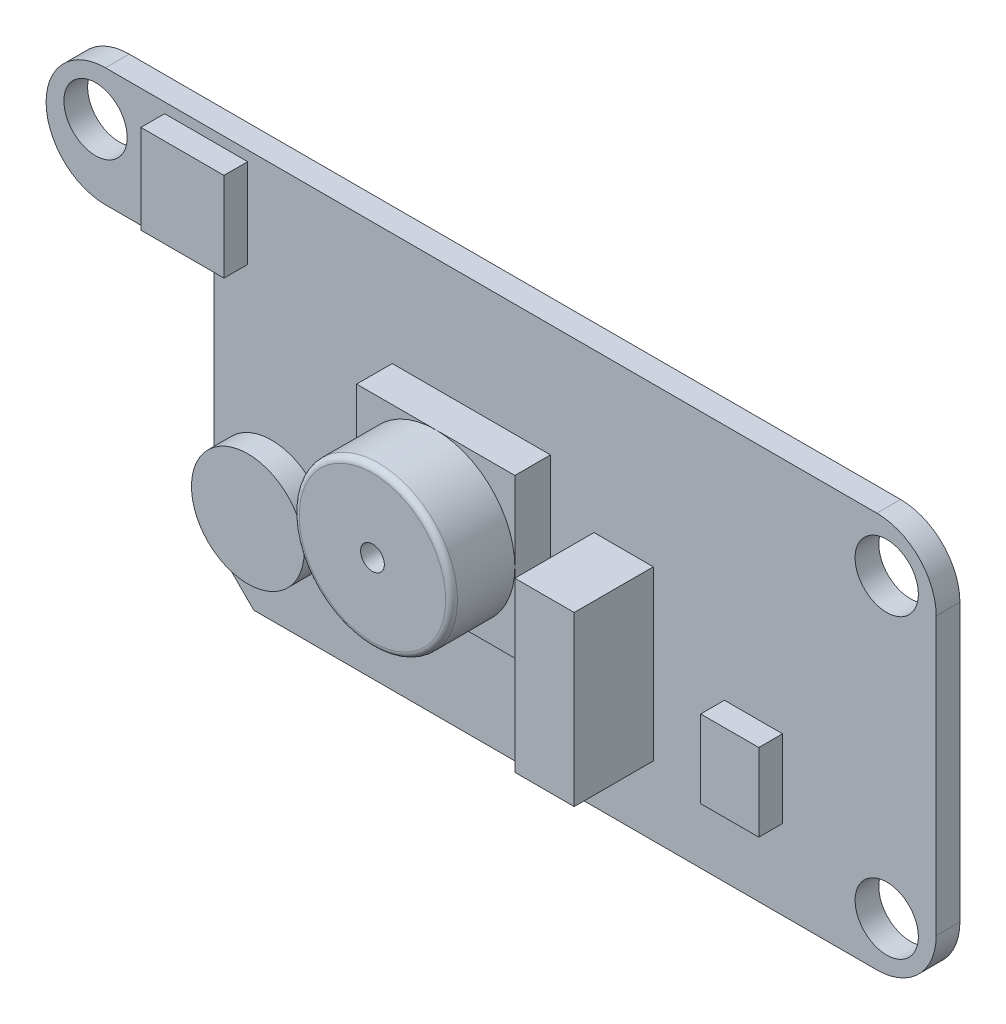
SolidWorks part; units mm, degrees
ref_plane "Front Plane" through (0, 0, 0) normal (0, 0, 1) x (1, 0, 0)
ref_plane "Top Plane" through (0, 0, 0) normal (0, 1, 0) x (1, 0, 0)
ref_plane "Right Plane" through (0, 0, 0) normal (1, 0, 0) x (0, 0, -1)
sketch "Sketch1" plane through (0, 0, 0) normal (0, 0, 1) x (1, 0, 0)
  line L0 (34, 2.5) -> (34, 17.5) construction
  line L1 (0, 0) -> (36.5, 0)
  line L2 (0, 0) -> (0, 14)
  line L3 (0, 20) -> (36.5, 20)
  line L4 (36.5, 0) -> (36.5, 20)
  line L5 (0, 20) -> (-8.5, 20)
  line L7 (0, 14) -> (-8.5, 14)
  line L8 (-8.5, 20) -> (-8.5, 14)
  line L9 (-6, 17.5) -> (33.3159, 17.5) construction
  circle A0 centre (34, 17.5) radius 1.6
  circle A1 centre (34, 2.5) radius 1.6
  circle A2 centre (-6, 17.5) radius 1.6
  dimension "D5" = 3.2
  dimension "D7" = 2.5
  dimension "D1" = 20
  dimension "D2" = 36.5
  dimension "D3" = 6
  dimension "D4" = 8.5
  dimension "D6" = 2.5
  dimension "D8" = 2.5
  dimension "D9" = 2.5
extrude "Boss-Extrude1" add sketch "Sketch1" along normal blind 1.2 contours L5 L8 L7 L2 L1 L4 L3 A2 A1 A0 region at (16.6569, 10.392, 0)
sketch "Sketch2" plane through (0, 0, 1.2) normal (0, 0, 1) x (1, 0, 0)
  line L0 (0, 0) -> (0, 14) construction
  line L1 (-2.5081, 19.4854) -> (1.6919, 19.4854)
  line L2 (-2.5081, 19.4854) -> (-2.5081, 14.9854)
  line L3 (-2.5081, 14.9854) -> (1.6919, 14.9854)
  line L4 (1.6919, 19.4854) -> (1.6919, 14.9854)
  line L5 (25.795, 7.9554) -> (28.7329, 7.9554)
  line L6 (25.795, 7.9554) -> (25.795, 4.0281)
  line L7 (25.795, 4.0281) -> (28.7329, 4.0281)
  line L8 (28.7329, 7.9554) -> (28.7329, 4.0281)
  circle A0 centre (2.9, 5.0499) radius 2.85
  dimension "D3" = 5.7
  dimension "D1" = 4.2
  dimension "D2" = 4.5
  dimension "D4" = 2.9
extrude "Boss-Extrude2" add sketch "Sketch2" along normal blind 1.2 contours A0 | L8 L5 L6 L7 | L3 L4 L1 L2 region at (27.264, 5.9918, 1.2) region at (2.9, 5.0499, 1.2)
sketch "Sketch3" plane through (0, 0, 1.2) normal (0, 0, 1) x (1, 0, 0)
  line L0 (0, 0) -> (0, 14) construction
  line L1 (9, 14.3) -> (17, 14.3)
  line L2 (9, 14.3) -> (9, 6.3)
  line L3 (9, 6.3) -> (17, 6.3)
  line L4 (17, 14.3) -> (17, 6.3)
  line L5 (36.5, 20) -> (-8.5, 20) construction
  dimension "D1" = 9
  dimension "D2" = 5.7
  dimension "D3" = 8
  dimension "D4" = 8
extrude "Boss-Extrude3" add sketch "Sketch3" along normal blind 1.8
sketch "Sketch4" plane through (0, 0, 3) normal (0, 0, 1) x (1, 0, 0)
  line L0 (9, 14.3) -> (17, 6.3) construction
  line L1 (9, 6.3) -> (17, 6.3) construction
  circle A0 centre (13, 10.3) radius 4
extrude "Boss-Extrude4" add sketch "Sketch4" along normal blind 3.2
sketch "Sketch5" plane through (0, 0, 6.2) normal (0, 0, 1) x (1, 0, 0)
  circle A0 centre (13, 10.3) radius 0.6
extrude "Cut-Extrude1" cut sketch "Sketch5" against normal blind 1
sketch "Sketch7" plane through (0, 0, 0) normal (0, 0, -1) x (-1, 0, 0)
  line L0 (0, 0) -> (0, 14) construction
  line L1 (-14, 14.5) -> (-7, 14.5)
  line L2 (-14, 14.5) -> (-14, 7.5)
  line L3 (-14, 7.5) -> (-7, 7.5)
  line L4 (-7, 14.5) -> (-7, 7.5)
  line L5 (0, 0) -> (-36.5, 0) construction
  line L7 (-23.0048, 2.8546) -> (-19.2766, 2.8546)
  line L8 (-23.0048, 2.8546) -> (-23.0048, 1.093)
  line L9 (-23.0048, 1.093) -> (-19.2766, 1.093)
  line L10 (-19.2766, 2.8546) -> (-19.2766, 1.093)
  line L11 (-23.0048, 3.6067) -> (-19.2766, 3.6067)
  line L12 (-23.0048, 3.6067) -> (-23.0048, 5.3113)
  line L13 (-23.0048, 5.3113) -> (-19.2766, 5.3113)
  line L14 (-19.2766, 3.6067) -> (-19.2766, 5.3113)
  line L15 (-21.1407, 17.7064) -> (-17.5374, 17.7064)
  line L16 (-21.1407, 17.7064) -> (-21.1407, 15.938)
  line L17 (-21.1407, 15.938) -> (-17.5374, 15.938)
  line L18 (-17.5374, 17.7064) -> (-17.5374, 15.938)
  line L19 (-8.0118, 5.8312) -> (-4.6597, 5.8312)
  line L20 (-8.0118, 5.8312) -> (-8.0118, 4.0988)
  line L21 (-8.0118, 4.0988) -> (-4.6597, 4.0988)
  line L22 (-4.6597, 5.8312) -> (-4.6597, 4.0988)
  line L23 (0, 18.7884) -> (1.2124, 18.7884)
  line L24 (0, 18.7884) -> (0, 16.1742)
  line L25 (0, 16.1742) -> (1.2124, 16.1742)
  line L26 (1.2124, 18.7884) -> (1.2124, 16.1742)
  line L27 (-19.8473, 15.3959) -> (-17.5374, 15.3959)
  line L28 (-19.8473, 15.3959) -> (-19.8473, 14.5)
  line L29 (-19.8473, 14.5) -> (-17.5374, 14.5)
  line L30 (-17.5374, 15.3959) -> (-17.5374, 14.5)
  line L31 (-26.6657, 4.965) -> (-24.1968, 4.965)
  line L32 (-26.6657, 4.965) -> (-26.6657, 3.8448)
  line L33 (-26.6657, 3.8448) -> (-24.1968, 3.8448)
  line L34 (-24.1968, 4.965) -> (-24.1968, 3.8448)
  line L35 (-26.6657, 2.4351) -> (-24.1968, 2.4351)
  line L36 (-26.6657, 2.4351) -> (-26.6657, 1.4687)
  line L37 (-26.6657, 1.4687) -> (-24.1968, 1.4687)
  line L38 (-24.1968, 2.4351) -> (-24.1968, 1.4687)
  dimension "D1" = 7
  dimension "D2" = 7
  dimension "D3" = 7.5
extrude "Boss-Extrude5" add sketch "Sketch7" along normal blind 1.2
sketch "Sketch8" plane through (0, 0, 1.2) normal (0, 0, 1) x (1, 0, 0)
  line L0 (17, 6.3) -> (17, 10.3) construction
  line L1 (19.2, 12) -> (22.2, 12)
  line L2 (19.2, 12) -> (19.2, 3.5)
  line L3 (19.2, 3.5) -> (22.2, 3.5)
  line L4 (22.2, 12) -> (22.2, 3.5)
  line L5 (0, 0) -> (36.5, 0) construction
  dimension "D1" = 3
  dimension "D2" = 8.5
  dimension "D3" = 2.2
  dimension "D4" = 3.5
extrude "Boss-Extrude6" add sketch "Sketch8" along normal blind 4
fillet "Fillet1" radius 0.3 1 edges at (17, 10.3, 6.2)
fillet "Fillet2" radius 3 4 edges at (36.5, 20, 0.6) (36.5, 0, 0.6) (-8.5, 14, 0.6) (-8.5, 20, 0.6)
chamfer "Chamfer1" distance 2 angle 45 1 edges at (0, 0, 0.6)
